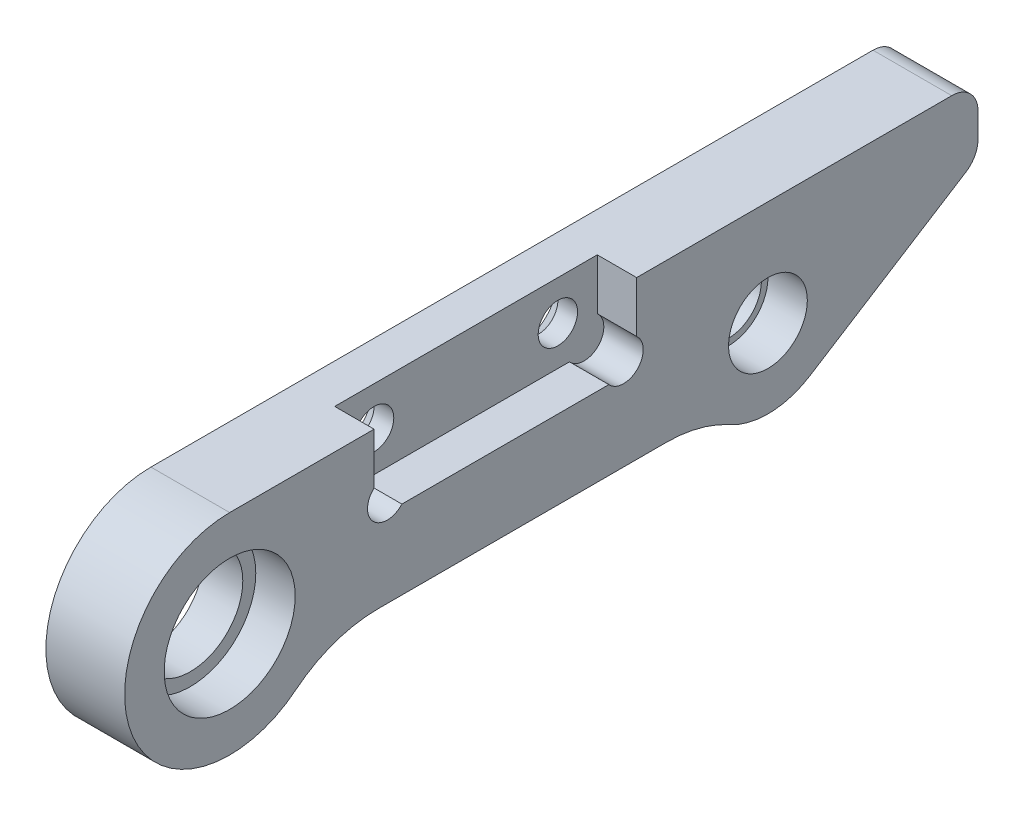
SolidWorks part; units mm, degrees
material "1060 Alloy"
ref_plane "Front Plane" through (0, 0, 0) normal (0, 0, 1) x (1, 0, 0)
ref_plane "Top Plane" through (0, 0, 0) normal (0, 1, 0) x (1, 0, 0)
ref_plane "Right Plane" through (0, 0, 0) normal (1, 0, 0) x (0, 0, -1)
sketch "Sketch27" plane through (0, 0, 0) normal (1, 0, 0) x (0, 0, -1)
  line L2 (9, 50) -> (66, 50)
  line L3 (9, 42) -> (30.9317, 42) construction
  line L4 (30.9317, 42) -> (30.9317, 54) construction
  line L6 (9, 34) -> (48.5644, 34)
  line L7 (30.9317, 54) -> (9, 42) construction
  line L8 (0, 0) -> (60, 0) construction
  line L9 (0, 0) -> (0, 58) construction
  line L10 (0, 58) -> (60, 58) construction
  line L11 (60, 0) -> (60, 58) construction
  line L12 (66, 50) -> (66, 45)
  line L13 (48.5644, 34) -> (66, 45)
  arc A0 (9, 50) -> (9, 34) centre (9, 42) ccw
  circle A1 centre (50, 42) radius 6 construction
  circle A3 centre (9, 42) radius 5.6 construction
  circle A5 centre (9, 42) radius 4
  circle A6 centre (50, 42) radius 2.5
  dimension "D9" = 12
  dimension "D10" = 5
  dimension "D12" = 8
  dimension "D13" = 8
  dimension "D14" = 5
  dimension "D6" = 16
  dimension "D16" = 11.2
  dimension "D1" = 60
  dimension "D2" = 58
  dimension "D3" = 42
  dimension "D4" = 9
  dimension "D5" = 50
  dimension "D7" = 42
  dimension "D8" = 12
  dimension "D17" = 25
extrude "Boss-Extrude1" add sketch "Sketch27" along normal blind 6
sketch "Sketch33" plane through (6, 0, 0) normal (1, 0, 0) x (0, 0, -1)
  circle A0 centre (9, 42) radius 4.99
  dimension "D1" = 9.98
extrude "Cut-Extrude2" cut sketch "Sketch33" against normal blind 3
sketch "Sketch34" plane through (6, 0, 0) normal (1, 0, 0) x (0, 0, -1)
  line L0 (20, 44) -> (40, 44)
  line L1 (20, 44) -> (20, 50)
  line L2 (40, 44) -> (40, 50)
  line L3 (20, 50) -> (40, 50)
  line L5 (9, 42) -> (43.3727, 42) construction
  circle A0 centre (50, 42) radius 2.5 construction
  dimension "D1" = 20
  dimension "D2" = 6
  dimension "D3" = 10
  dimension "D4" = 2
extrude "Cut-Extrude3" cut sketch "Sketch34" against normal blind 3
sketch "Sketch36" plane through (3, 0, 0) normal (1, 0, 0) x (0, 0, -1)
  line L0 (20, 50) -> (20, 44) construction
  line L2 (40, 44) -> (40, 50) construction
  line L3 (20, 44) -> (40, 44) construction
  circle A0 centre (23, 47) radius 1.5
  circle A1 centre (37, 47) radius 1.5
  dimension "D1" = 3
  dimension "D2" = 3
  dimension "D3" = 3
  dimension "D5" = 3
extrude "Cut-Extrude5" cut sketch "Sketch36" against normal up to next
fillet "Fillet3" radius 2 2 edges at (3, 50, -66) (3, 45, -66)
fillet "Fillet4" radius 10 1 edges at (3, 34, -48.5644)
sketch "Sketch37" plane through (6, 0, 0) normal (1, 0, 0) x (0, 0, -1)
  line L1 (9, 34) -> (45.6736, 34) construction
  line L2 (20.3137, 38) -> (42.254, 38)
  line L3 (51.0093, 35.5425) -> (65.0672, 44.4115) construction
  line L4 (9, 34) -> (53.2015, 34)
  line L5 (53.2015, 34) -> (53.2015, 36.9255)
  line L6 (20, 44) -> (40, 44) construction
  arc A0 (9, 34) -> (14.0283, 35.7778) centre (9, 42) ccw
  arc A1 (14.0283, 35.7778) -> (20.3137, 38) centre (20.3137, 28) cw
  arc A2 (42.254, 38) -> (47.0953, 36.75) centre (42.254, 28) cw
  arc A3 (47.0953, 36.75) -> (53.2015, 36.9255) centre (50, 42) ccw
  circle A4 centre (50, 42) radius 2.5 construction
  circle A5 centre (9, 42) radius 4.99 construction
  dimension "D2" = 10
  dimension "D1" = 6
extrude "Cut-Extrude6" cut sketch "Sketch37" against normal up to next
chamfer "Chamfer1" distance 1.5 angle 45 2 edges at (0, 47, -24.5) (0, 47, -38.5)
sketch "Sketch38" plane through (6, 0, 0) normal (1, 0, 0) x (0, 0, -1)
  circle A0 centre (50, 42) radius 3
  dimension "D1" = 6
extrude "Cut-Extrude7" cut sketch "Sketch38" against normal blind 3
sketch "Sketch39" plane through (6, 0, 0) normal (1, 0, 0) x (0, 0, -1)
  line L0 (20, 44) -> (40, 44) construction
  line L1 (20, 50) -> (20, 44) construction
  line L2 (40, 44) -> (40, 50) construction
  circle A0 centre (21, 45) radius 1.5
  circle A1 centre (39, 45) radius 1.5
  dimension "D1" = 3
  dimension "D2" = 1
  dimension "D3" = 1
  dimension "D4" = 1
extrude "Cut-Extrude8" cut sketch "Sketch39" against normal up to surface (3 mm away) up to face at (3, 47, -38.5)
